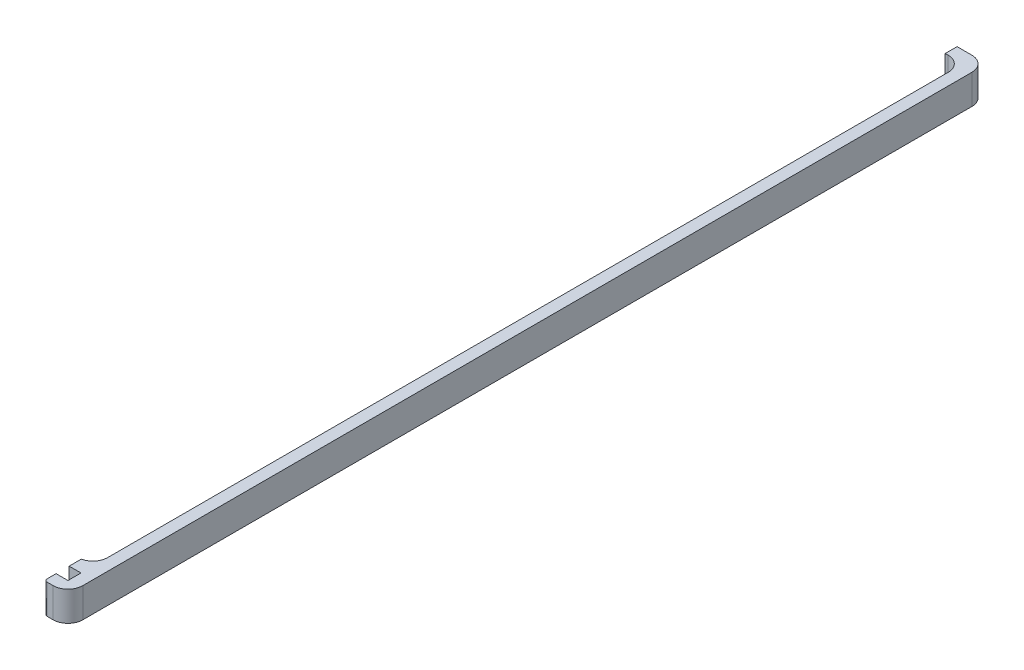
SolidWorks part; units mm, degrees
ref_plane "Front Plane" through (0, 0, 0) normal (0, 0, 1) x (1, 0, 0)
ref_plane "Top Plane" through (0, 0, 0) normal (0, 1, 0) x (1, 0, 0)
ref_plane "Right Plane" through (0, 0, 0) normal (1, 0, 0) x (0, 0, -1)
sketch "Sketch1" plane through (0, 0, 0) normal (0, 1, 0) x (1, 0, 0)
  line L1 (-19.5, 77.5) -> (19.5, 77.5)
  line L2 (-19.5, 77.5) -> (-19.5, -77.5)
  line L3 (-19.5, -77.5) -> (19.5, -77.5)
  line L4 (19.5, 77.5) -> (19.5, -77.5)
  line L5 (-19.5, 77.5) -> (19.5, -77.5) construction
  line L6 (-19.5, -77.5) -> (19.5, 77.5) construction
  point P0 (0, 0)
  dimension "D1" = 39
  dimension "D2" = 155
extrude "Boss-Extrude1" add sketch "Sketch1" along normal blind 2
sketch "Sketch2" plane through (0, 2, 0) normal (0, 1, 0) x (1, 0, 0)
  line L0 (-17.5, -75.5) -> (-17.5, -77.5)
  line L1 (-19.5, 77.5) -> (19.5, 77.5)
  line L2 (-19.5, 77.5) -> (-19.5, -77.5)
  line L3 (-19.5, -77.5) -> (19.5, -77.5)
  line L4 (19.5, 77.5) -> (19.5, -77.5)
  line L5 (-17.5, 75.5) -> (17.5, 75.5)
  line L6 (-17.5, 75.5) -> (-17.5, -75.5)
  line L7 (-17.5, -75.5) -> (17.5, -75.5)
  line L8 (17.5, 75.5) -> (17.5, -75.5)
  line L9 (-17.5, 75.5) -> (17.5, -75.5) construction
  line L10 (-17.5, -75.5) -> (17.5, 75.5) construction
  line L11 (17.5, -75.5) -> (17.5, -77.5)
  point P6 (0, 0)
  line M9 (19.5, -77.5) -> (19.5, 77.5)
  line M10 (19.5, 77.5) -> (-19.5, 77.5)
  line M11 (-19.5, 77.5) -> (-19.5, -77.5)
  line M12 (-19.5, -77.5) -> (19.5, -77.5)
  dimension "D1" = 2
  dimension "D2" = 2
extrude "Boss-Extrude2" add sketch "Sketch2" along normal blind 38 contours L8 L11 L3 L0 L6 L5 M9 M10 M11 M12 region at (-19.0983, 2, 76.5)
sketch "Sketch3" plane through (0, 2, 0) normal (0, 1, 0) x (1, 0, 0)
  line L0 (-17.5, 75.5) -> (-17.5, -77.5) construction
  line L1 (-17.5, -77.5) -> (-15.5, -77.5)
  line L2 (-17.5, -77.5) -> (-17.5, -75.5)
  line L3 (-17.5, -75.5) -> (-15.5, -75.5)
  line L4 (-15.5, -77.5) -> (-15.5, -75.5)
  line L5 (-17.5, -73.3) -> (-15.5, -73.3)
  line L6 (-17.5, -73.3) -> (-17.5, -71.3)
  line L7 (-17.5, -71.3) -> (-15.5, -71.3)
  line L8 (-15.5, -73.3) -> (-15.5, -71.3)
  line L9 (17.5, 75.5) -> (17.5, -77.5) construction
  line L10 (17.5, -77.5) -> (15.5, -77.5)
  line L11 (17.5, -77.5) -> (17.5, -75.5)
  line L12 (17.5, -75.5) -> (15.5, -75.5)
  line L13 (15.5, -77.5) -> (15.5, -75.5)
  line L14 (17.5, -73.3) -> (15.5, -73.3)
  line L15 (17.5, -73.3) -> (17.5, -71.3)
  line L16 (17.5, -71.3) -> (15.5, -71.3)
  line L17 (15.5, -73.3) -> (15.5, -71.3)
  line L18 (15.5, -75.5) -> (15.5, -73.3) construction
  line L19 (-15.5, -73.3) -> (15.5, -73.3) construction
  line L20 (-15.5, -75.5) -> (-15.5, -73.3) construction
  line L21 (-15.5, -75.5) -> (15.5, -75.5) construction
  line L22 (15.5, -71.3) -> (-15.5, -71.3) construction
  dimension "D1" = 2
  dimension "D2" = 2
  dimension "D3" = 2.2
  dimension "D4" = 2
extrude "Boss-Extrude3" add sketch "Sketch3" along normal up to surface (38 mm away) up to face at (0, 40, 0.5)
sketch "Sketch4" plane through (0, 0, -75.5) normal (0, 0, 1) x (1, 0, 0)
  line L0 (-17.5, 40) -> (-15.5, 40)
  line L1 (-17.5, 40) -> (17.5, 40) construction
  line L2 (-15.5, 40) -> (-15.5, 38)
  line L3 (-15.5, 38) -> (-17.5, 38)
  line L5 (-17.5, 38) -> (-17.5, 40)
  line L7 (-17.5, 40) -> (-17.5, 2) construction
  line L8 (-15.5, 33.8) -> (-17.5, 31.8)
  line L9 (-17.5, 31.8) -> (-17.5, 35.8)
  line L10 (-15.5, 33.8) -> (-15.5, 35.8)
  line L11 (-15.5, 35.8) -> (-17.5, 35.8)
  line L12 (0, 0) -> (0, 40) construction
  line L13 (15.5, 35.8) -> (17.5, 35.8)
  line L14 (15.5, 33.8) -> (15.5, 35.8)
  line L15 (17.5, 31.8) -> (17.5, 35.8)
  line L16 (15.5, 33.8) -> (17.5, 31.8)
  line L17 (17.5, 38) -> (17.5, 40)
  line L18 (15.5, 38) -> (17.5, 38)
  line L19 (15.5, 40) -> (15.5, 38)
  line L20 (17.5, 40) -> (15.5, 40)
  dimension "D1" = 2
  dimension "D2" = 2
  dimension "D3" = 45
  dimension "D4" = 2.2
  dimension "D5" = 2
extrude "Boss-Extrude4" add sketch "Sketch4" along normal up to surface (153 mm away) up to face at (0, 20.5, 77.5)
sketch "Sketch5" plane through (0, 2, 0) normal (0, 1, 0) x (1, 0, 0)
  line L1 (-15.5, -77.5) -> (15.5, -77.5)
  line L2 (-15.5, -77.5) -> (-15.5, -75.5)
  line L3 (-15.5, -75.5) -> (15.5, -75.5)
  line L4 (15.5, -77.5) -> (15.5, -75.5)
  line L5 (-15.5, -71.3) -> (15.5, -71.3)
  line L6 (-15.5, -71.3) -> (-15.5, -73.3)
  line L7 (-15.5, -73.3) -> (15.5, -73.3)
  line L8 (15.5, -71.3) -> (15.5, -73.3)
sketch "Sketch6" plane through (0, 0, -75.5) normal (0, 0, 1) x (1, 0, 0)
  line L0 (-17.5, 38) -> (-15.5, 38) construction
  line L1 (-17.5, 38) -> (17.5, 38)
  line L2 (-17.5, 38) -> (-17.5, 35.8)
  line L3 (-17.5, 35.8) -> (17.5, 35.8)
  line L4 (17.5, 38) -> (17.5, 35.8)
  line L5 (-17.5, 38) -> (-17.5, 35.8) construction
  line L6 (-15.5, 35.8) -> (-17.5, 35.8) construction
extrude "Cut-Extrude1" cut sketch "Sketch6" along normal through all
sketch "Sketch7" plane through (0, 2, 0) normal (0, 1, 0) x (1, 0, 0)
  line L1 (-17.5, -75.5) -> (17.5, -75.5)
  line L2 (-17.5, -75.5) -> (-17.5, -73.3)
  line L3 (-17.5, -73.3) -> (17.5, -73.3)
  line L4 (17.5, -75.5) -> (17.5, -73.3)
extrude "Cut-Extrude2" cut sketch "Sketch7" along normal through all
extrude "Boss-Extrude5" add sketch "Sketch5" along normal blind 2
sketch "Sketch8" plane through (0, 0, 0) normal (1, 0, 0) x (0, 0, -1)
  line L0 (75.5, 40) -> (73.5, 40)
  line L1 (-73.3, 40) -> (75.5, 40) construction
  line L2 (73.5, 40) -> (73.5, 38)
  line L3 (-73.3, 38) -> (75.5, 38) construction
  line L4 (73.5, 38) -> (75.5, 38)
  line L5 (75.5, 38) -> (75.5, 40)
  line L6 (75.5, 35.8) -> (73.5, 35.8)
  line L7 (-73.3, 35.8) -> (75.5, 35.8) construction
  line L8 (73.5, 35.8) -> (73.5, 33.8)
  line L9 (-71.3, 33.8) -> (75.5, 33.8) construction
  line L10 (73.5, 33.8) -> (75.5, 31.8)
  line L11 (75.5, 31.8) -> (75.5, 35.8)
  dimension "D1" = 2
extrude "Boss-Extrude6" add sketch "Sketch8" along normal up to surface and the other way up to surface up to face at (17.5, 16.9, -2.1) other way up to face at (-17.5, 16.9, -2.1)
sketch "Sketch10" plane through (-17.5, 0, 0) normal (1, 0, 0) x (0, 0, -1)
  line L1 (-75.5, 35.8) -> (-77.5, 35.8)
  line L2 (-75.5, 35.8) -> (-75.5, 38)
  line L3 (-75.5, 38) -> (-77.5, 38)
  line L4 (-77.5, 35.8) -> (-77.5, 38)
  line L5 (-73.3, 40) -> (-75.5, 40)
  line L6 (-73.3, 40) -> (-73.3, 38)
  line L7 (-73.3, 38) -> (-75.5, 38)
  line L8 (-75.5, 40) -> (-75.5, 38)
  line M1 (-75.5, 40) -> (-75.5, 38)
  line M2 (-75.5, 38) -> (-77.5, 38)
  line M3 (-77.5, 38) -> (-77.5, 35.8)
  line M4 (-77.5, 35.8) -> (-75.5, 35.8)
  line M11 (-73.3, 38) -> (-73.3, 40)
  line M12 (-73.3, 40) -> (-75.5, 40)
extrude "Boss-Extrude8" add sketch "Sketch10" along normal up to surface (2 mm away) contours L2 M4 M2 M3 | L7 M11 M12 M1 region at (-17.5, 39, 74.4) region at (-17.5, 36.9, 76.5) up to face at (-15.5, 39, -0.1)
sketch "Sketch11" plane through (17.5, 0, 0) normal (-1, 0, 0) x (0, 0, 1)
  line L1 (75.5, 35.8) -> (77.5, 35.8)
  line L2 (75.5, 35.8) -> (75.5, 38)
  line L3 (75.5, 38) -> (77.5, 38)
  line L4 (77.5, 35.8) -> (77.5, 38)
  line L5 (73.3, 40) -> (75.5, 40)
  line L6 (73.3, 40) -> (73.3, 38)
  line L7 (73.3, 38) -> (75.5, 38)
  line L8 (75.5, 40) -> (75.5, 38)
  line M2 (75.5, 35.8) -> (77.5, 35.8)
  line M3 (77.5, 35.8) -> (77.5, 38)
  line M4 (77.5, 38) -> (75.5, 38)
  line M5 (75.5, 38) -> (75.5, 40)
  line M6 (75.5, 40) -> (73.3, 40)
  line M7 (73.3, 40) -> (73.3, 38)
extrude "Boss-Extrude9" add sketch "Sketch11" along normal up to surface (2 mm away) contours L2 M2 M3 M4 | L7 M7 M5 M6 region at (17.5, 36.9, 76.5) region at (17.5, 39, 74.4) up to face at (15.5, 39, -0.1)
fillet "Fillet2" radius 2.5 17 edges at (-17.5, 16.9, 71.3) (17.5, 16.9, 71.3) (19.5, 20, 77.5) (-19.5, 20, 77.5) (-19.5, 20, -77.5) (-17.5, 16.9, -75.5) (17.5, 16.9, -75.5) (19.5, 20, -77.5) (-19.5, 40, 0) (0, 40, -77.5) (19.5, 40, 0) (0, 0, -77.5) (0, 0, 77.5) (-19.5, 0, 0) (19.5, 0, 0) (-17.5, 40, 77.5) (17.5, 40, 77.5)
sketch "Sketch13" plane through (0, 0, -77.5) normal (0, 0, -1) x (-1, 0, 0)
  line L0 (15.5, 37.5) -> (15.5, 4) construction
  line L1 (-15.5, 7) -> (15.5, 7)
  line L2 (-15.5, 7) -> (-15.5, 4)
  line L3 (-15.5, 4) -> (15.5, 4)
  line L4 (15.5, 7) -> (15.5, 4)
  dimension "D1" = 3
sketch "Sketch14" plane through (0, 0, -75.5) normal (0, 0, 1) x (1, 0, 0)
  line L1 (-18.25, 9) -> (18.25, 9)
  line L2 (-18.25, 9) -> (-18.25, 1.25)
  line L3 (-18.25, 1.25) -> (18.25, 1.25)
  line L4 (18.25, 9) -> (18.25, 1.25)
  line L5 (15.5, 7) -> (-15.5, 7) construction
  line L7 (17, 0) -> (17, 2.5) construction
  line L8 (19.5, 2.5) -> (17, 2.5) construction
  line L10 (-19.5, 2.5) -> (-17, 2.5) construction
  point P20 (17, 1.25)
  point P23 (18.25, 2.5)
  point P26 (-18.25, 2.5)
  dimension "D1" = 2
extrude "Boss-Extrude10" add sketch "Sketch14" along normal blind 2
extrude "Cut-Extrude4" cut sketch "Sketch13" against normal blind 2
fillet "Fillet3" radius 2 1 edges at (0, 9, -73.5)
fillet "Fillet4" radius 0.5 12 edges at (0, 4, -77.5) (0, 7, -77.5) (15.5, 7, -76.5) (15.5, 4, -76.5) (15.5, 5.5, -77.5) (-15.5, 4, -76.5) (-15.5, 7, -76.5) (-15.5, 5.5, -77.5) (0, 7, -75.5) (-15.5, 5.5, -75.5) (0, 4, -75.5) (15.5, 5.5, -75.5)
sketch "Sketch15" plane through (0, 0, 0) normal (0, -1, 0) x (1, 0, 0)
  line L0 (0, 77.5) -> (0, 0) construction
  line L1 (-17, 77.5) -> (17, 77.5) construction
  line L2 (0, 0) -> (0, -77.5) construction
  line L4 (17, -77.5) -> (-17, -77.5) construction
  circle A0 centre (0, 38.75) radius 5.1
  circle A1 centre (0, -38.75) radius 5.1
  dimension "D1" = 10.2
extrude "Cut-Extrude5" cut sketch "Sketch15" against normal through all
sketch "Sketch16" plane through (0, 2, 0) normal (0, 1, 0) x (1, 0, 0)
  circle A0 centre (0, 38.75) radius 7.1
  circle A1 centre (0, -38.75) radius 7.1
  circle A2 centre (0, 38.75) radius 5.1 construction
  dimension "D1" = 2
extrude "Boss-Extrude11" add sketch "Sketch16" along normal blind 1
fillet "Fillet5" radius 0.5 4 edges at (0, 2, 45.85) (0, 2, -31.65) (0, 3, 45.85) (0, 3, -31.65)
sketch "Sketch12" plane through (0, 0, -75.5) normal (0, 0, 1) x (1, 0, 0)
  line L0 (0, 0) -> (0, 40) construction
  line L1 (15.5, 40) -> (-15.5, 40) construction
  line L2 (0, 20) -> (-10, 20)
  line L3 (0, 20) -> (-9.0097, 15.6612)
  line L4 (0, 20) -> (-6.2349, 12.1817)
  line L5 (0, 20) -> (-2.2252, 10.2507)
  line L6 (0, 20) -> (2.2252, 10.2507)
  line L7 (0, 20) -> (6.2349, 12.1817)
  line L8 (0, 20) -> (9.0097, 15.6612)
  line L9 (0, 20) -> (10, 20)
  line L10 (0, 20) -> (9.0097, 24.3388)
  line L11 (0, 20) -> (6.2349, 27.8183)
  line L12 (0, 20) -> (2.2252, 29.7493)
  line L13 (0, 20) -> (-2.2252, 29.7493)
  line L14 (0, 20) -> (-6.2349, 27.8183)
  line L15 (0, 20) -> (-9.0097, 24.3388)
  circle A0 centre (0, 20) radius 10
  circle A1 centre (0, 20) radius 7.5
  circle A2 centre (0, 20) radius 5
  circle A3 centre (0, 20) radius 2.5
  point P26 (0, 20)
  dimension "D1" = 20
  dimension "D2" = 2.5
  dimension "D3" = 2.5
  dimension "D4" = 2.5
  dimension "D5" = 14
extrude "Cut-Extrude3" cut sketch "Sketch12" against normal through all contours A1 L6 A0 L7 | A1 L4 A0 L5 | A1 L2 A0 L3 | A1 L14 A0 L15 | A1 L0 A0 L13 | L0 A1 L12 A0 | A1 L10 A0 L11 | A1 L8 A0 L9 | A3 L8 A2 L9 | A3 L10 A2 L11 | L0 A3 L12 A2 | A3 L0 A2 L13 | A3 L14 A2 L15 | A3 L2 A2 L3 | A3 L4 A2 L5 | A3 L6 A2 L7 region at (-3.7903, 12.1293, -75.5) region at (3.7903, 12.1293, -75.5) region at (-1.6732, 16.5256, -75.5) region at (1.6732, 16.5256, -75.5) region at (-8.5168, 18.0561, -75.5) region at (8.5168, 18.0561, -75.5) region at (-0.4345, 23.8563, -75.5) region at (0.4345, 23.8563, -75.5) region at (-3.7596, 19.1419, -75.5) region at (3.7596, 19.1419, -75.5) region at (3.015, 22.4044, -75.5) region at (-3.015, 22.4044, -75.5) region at (-6.8299, 25.4467, -75.5) region at (6.8299, 25.4467, -75.5) region at (-0.9843, 28.7358, -75.5) region at (0.9843, 28.7358, -75.5)
fillet "Fillet6" radius 0.4 112 edges at (5.4555, 26.841, -77.5) (7.8183, 26.2349, -77.5) (7.8835, 23.7965, -77.5) (5.8637, 24.6762, -77.5) (3.75, 20, -77.5) (4.8746, 18.8874, -77.5) (3.3786, 18.3729, -77.5) (2.4373, 19.4437, -77.5) (-1.9471, 28.5306, -77.5) (0, 30, -77.5) (1.9471, 28.5306, -77.5) (0, 27.5, -77.5) (-7.8835, 16.2035, -77.5) (-9.7493, 17.7748, -77.5) (-8.75, 20, -77.5) (-7.312, 18.3311, -77.5) (2.3381, 17.0681, -77.5) (2.1694, 15.4952, -77.5) (0.8345, 16.344, -77.5) (1.0847, 17.7476, -77.5) (-0.8345, 16.344, -77.5) (-2.1694, 15.4952, -77.5) (-2.3381, 17.0681, -77.5) (-1.0847, 17.7476, -77.5) (5.4555, 13.159, -77.5) (4.3388, 10.9903, -77.5) (1.9471, 11.4694, -77.5) (3.2541, 13.2427, -77.5) (0, 22.5, -77.5) (-0.8345, 23.656, -77.5) (0, 25, -77.5) (0.8345, 23.656, -77.5) (-3.3786, 21.6271, -77.5) (-3.9092, 23.1174, -77.5) (-2.3381, 22.9319, -77.5) (-1.9546, 21.5587, -77.5) (-3.3786, 18.3729, -77.5) (-4.8746, 18.8874, -77.5) (-3.75, 20, -77.5) (-2.4373, 19.4437, -77.5) (-1.9471, 11.4694, -77.5) (-4.3388, 10.9903, -77.5) (-5.4555, 13.159, -77.5) (-3.2541, 13.2427, -77.5) (-7.8835, 23.7965, -77.5) (-7.8183, 26.2349, -77.5) (-5.4555, 26.841, -77.5) (-5.8637, 24.6762, -77.5) (2.3381, 22.9319, -77.5) (3.9092, 23.1174, -77.5) (3.3786, 21.6271, -77.5) (1.9546, 21.5587, -77.5) (8.75, 20, -77.5) (9.7493, 17.7748, -77.5) (7.8835, 16.2035, -77.5) (7.312, 18.3311, -77.5) (7.8835, 23.7965, -75.5) (7.8183, 26.2349, -75.5) (5.4555, 26.841, -75.5) (5.8637, 24.6762, -75.5) (3.3786, 18.3729, -75.5) (4.8746, 18.8874, -75.5) (3.75, 20, -75.5) (2.4373, 19.4437, -75.5) (1.9471, 28.5306, -75.5) (0, 30, -75.5) (-1.9471, 28.5306, -75.5) (0, 27.5, -75.5) (-8.75, 20, -75.5) (-9.7493, 17.7748, -75.5) (-7.8835, 16.2035, -75.5) (-7.312, 18.3311, -75.5) (0.8345, 16.344, -75.5) (2.1694, 15.4952, -75.5) (2.3381, 17.0681, -75.5) (1.0847, 17.7476, -75.5) (-2.3381, 17.0681, -75.5) (-2.1694, 15.4952, -75.5) (-0.8345, 16.344, -75.5) (-1.0847, 17.7476, -75.5) (1.9471, 11.4694, -75.5) (4.3388, 10.9903, -75.5) (5.4555, 13.159, -75.5) (3.2541, 13.2427, -75.5) (0, 22.5, -75.5) (0.8345, 23.656, -75.5) (0, 25, -75.5) (-0.8345, 23.656, -75.5) (-2.3381, 22.9319, -75.5) (-3.9092, 23.1174, -75.5) (-3.3786, 21.6271, -75.5) (-1.9546, 21.5587, -75.5) (-3.75, 20, -75.5) (-4.8746, 18.8874, -75.5) (-3.3786, 18.3729, -75.5) (-2.4373, 19.4437, -75.5) (-5.4555, 13.159, -75.5) (-4.3388, 10.9903, -75.5) (-1.9471, 11.4694, -75.5) (-3.2541, 13.2427, -75.5) (-5.4555, 26.841, -75.5) (-7.8183, 26.2349, -75.5) (-7.8835, 23.7965, -75.5) (-5.8637, 24.6762, -75.5) (3.3786, 21.6271, -75.5) (3.9092, 23.1174, -75.5) (2.3381, 22.9319, -75.5) (7.8835, 16.2035, -75.5) (9.7493, 17.7748, -75.5) (8.75, 20, -75.5) (7.312, 18.3311, -75.5) (1.9546, 21.5587, -75.5)
fillet "Fillet7" radius 0.5 8 edges at (15.5, 40, 0.75) (15.5, 39.2678, 76.7678) (-15.5, 40, 0.75) (-15.5, 39.2678, 76.7678) (0, 40, -73.5) (15.5, 20.75, 77.5) (-15.5, 20.75, 77.5) (0, 4, 77.5)
sketch "Sketch17" plane through (0, 0, 0) normal (0, -1, 0) x (1, 0, 0)
  line L0 (-17, -77.5) -> (-17, 70.3)
  line L1 (-17, -77.5) -> (17, -77.5)
  line L2 (17, -77.5) -> (17, 70.3)
  line L3 (17, -75) -> (17, 75) construction
  line L5 (17, 70.3) -> (15, 71.3)
  line L6 (15, 71.3) -> (15, 77.5)
  line L7 (15, 77.5) -> (-15, 77.5)
  line L8 (-15, 77.5) -> (-15, 71.3)
  line L9 (-15, 71.3) -> (-17, 70.3)
  line L10 (-17, 75) -> (-17, -75) construction
  line L12 (-15, 71.3) -> (15, 71.3) construction
  line L13 (17, 70.3) -> (-17, 70.3) construction
  line L14 (0, 71.3) -> (0, 77.5) construction
  line L15 (-17, 77.5) -> (17, 77.5) construction
  arc A0 (-19.5, -75) -> (-17, -77.5) centre (-17, -75) ccw construction
  dimension "D1" = 1
  dimension "D2" = 30
  dimension "D3" = 6.2
extrude "Cut-Extrude6" cut sketch "Sketch17" against normal blind 6
sketch "Sketch18" plane through (0, 0, 0) normal (0, 0, 1) x (1, 0, 0)
  line L0 (15, 9) -> (-15, 9) construction
  line L1 (-14.5, 9) -> (14.5, 9)
  line L2 (-14.5, 9) -> (-14.5, 6)
  line L3 (-14.5, 6) -> (14.5, 6)
  line L4 (14.5, 9) -> (14.5, 6)
  line L5 (-17, 6) -> (17, 6) construction
  line L6 (0, 6) -> (0, 0) construction
  dimension "D1" = 29
extrude "Cut-Extrude8" cut sketch "Sketch18" against normal through all
sketch "Sketch20" plane through (0, 0, 0) normal (0, 0, 1) x (1, 0, 0)
  line L0 (-16, 40) -> (16, 40) construction
  line L1 (-19.5, 40) -> (-14.5, 40)
  line L2 (-19.5, 40) -> (-19.5, 0)
  line L3 (-19.5, 0) -> (-14.5, 0)
  line L4 (-14.5, 40) -> (-14.5, 0)
  line L5 (-14.5, 6) -> (14.5, 6)
  line L6 (-14.5, 6) -> (-14.5, 40)
  line L7 (-14.5, 40) -> (14.5, 40)
  line L8 (14.5, 6) -> (14.5, 40)
  line L9 (14.5, 40) -> (19.5, 40)
  line L10 (14.5, 40) -> (14.5, 0)
  line L11 (14.5, 0) -> (19.5, 0)
  line L12 (19.5, 40) -> (19.5, 0)
  line L13 (-15, 0) -> (-17, 0) construction
  line L14 (-19.5, 2.5) -> (-19.5, 37.5) construction
  line L15 (17, 0) -> (15, 0) construction
  line L16 (19.5, 37.5) -> (19.5, 2.5) construction
extrude "Cut-Extrude11" cut sketch "Sketch20" against normal through all both and the other way through all contours L5 L8 L7 L4 | L1 L2 L3 L4 region at (0, 23, 0)
sketch "Sketch21" plane through (0, 0, 0) normal (1, 0, 0) x (0, 0, -1)
  line L1 (-77.5, 40) -> (77.5, 40)
  line L2 (-77.5, 40) -> (-77.5, 30)
  line L3 (-77.5, 30) -> (77.5, 30)
  line L4 (77.5, 40) -> (77.5, 30)
  line L5 (77.5, 30) -> (-77.5, 30)
  line L6 (77.5, 30) -> (77.5, 10)
  line L7 (77.5, 10) -> (-77.5, 10)
  line L8 (-77.5, 30) -> (-77.5, 10)
  line L9 (-77.5, 10) -> (77.5, 10)
  line L10 (-77.5, 10) -> (-77.5, 0)
  line L11 (-77.5, 0) -> (77.5, 0)
  line L12 (77.5, 10) -> (77.5, 0)
  line L16 (77.5, 30) -> (77.5, 10)
  line L17 (-77.5, 10) -> (-77.5, 30)
  line L18 (77.5, 37.5) -> (77.5, 6) construction
  line L19 (-75, 40) -> (75, 40) construction
  line L20 (-77.5, 2.5) -> (-77.5, 37.5) construction
  line L21 (75, 0) -> (-70.3, 0) construction
  dimension "D1" = 20
  dimension "D2" = 10
extrude "Cut-Extrude12" cut sketch "Sketch21" along normal through all contours L4 L1 L2 L3 | L12 L7 L10 L11 region at (0, 35, 0) region at (0, 5, 0)
sketch "Sketch22" plane through (19.5, 0, 0) normal (1, 0, 0) x (0, 0, -1)
  line L0 (77.5, 30) -> (77.5, 10) construction
  line L1 (-77.5, 10) -> (77.5, 10)
  line L2 (-77.5, 10) -> (-77.5, 25)
  line L3 (-77.5, 25) -> (77.5, 25)
  line L4 (77.5, 10) -> (77.5, 25)
  line L5 (-75, 30) -> (75, 30) construction
  dimension "D1" = 5
extrude "Cut-Extrude13" cut sketch "Sketch22" against normal through all
